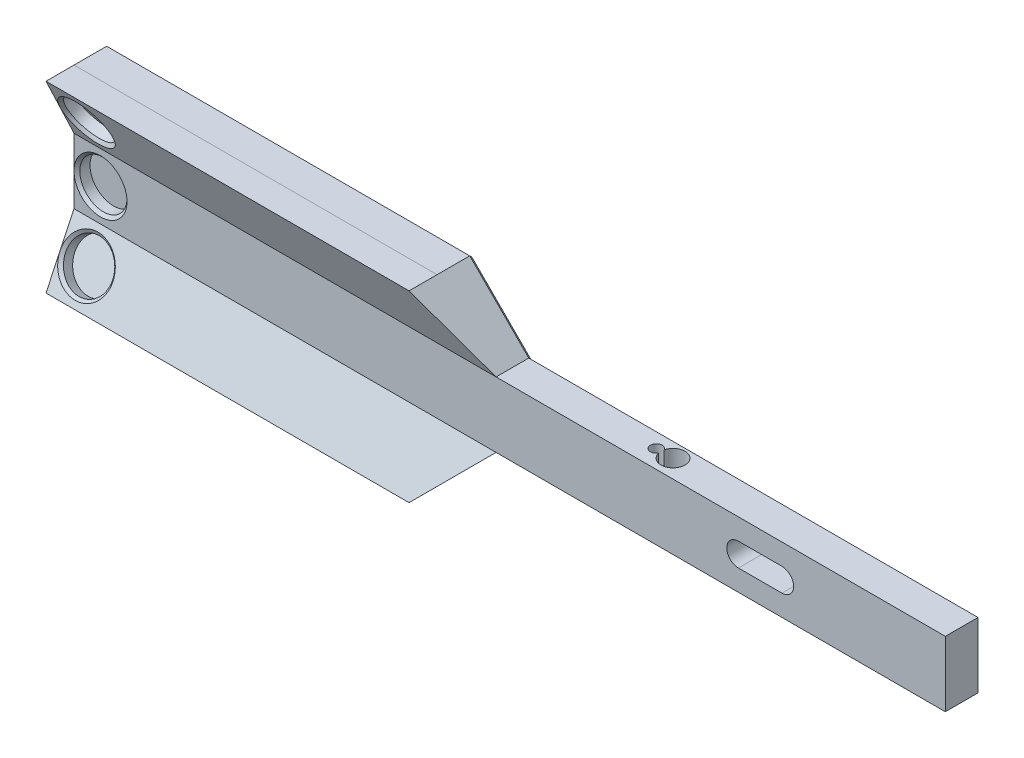
SolidWorks part; units mm, degrees
ref_plane "Front" through (0, 0, 0) normal (0, 0, 1) x (1, 0, 0)
ref_plane "Top" through (0, 0, 0) normal (0, 1, 0) x (1, 0, 0)
ref_plane "Right" through (0, 0, 0) normal (1, 0, 0) x (0, 0, -1)
sketch "Sketch1" plane through (0, 0, 0) normal (0, 0, 1) x (1, 0, 0)
  line L1 (60, -4.5) -> (-60, -4.5)
  line L2 (60, -4.5) -> (60, 4.5)
  line L3 (60, 4.5) -> (-60, 4.5)
  line L4 (-60, -4.5) -> (-60, 4.5)
  line L5 (60, -4.5) -> (-60, 4.5) construction
  line L6 (60, 4.5) -> (-60, -4.5) construction
  point P0 (0, 0)
  dimension "D1" = 9
  dimension "D2" = 120
extrude "Boss-Extrude1" add sketch "Sketch1" along normal blind 5
sketch "Sketch2" plane through (0, 4.5, 0) normal (0, 1, 0) x (1, 0, 0)
  line L0 (60, -5) -> (60, 0) construction
  line L2 (60, 0) -> (-60, 0) construction
  circle A0 centre (20, -2.5) radius 1.65
  dimension "D3" = 3.3
  dimension "D1" = 2.5
  dimension "D2" = 40
sketch "Sketch4" plane through (0, 0, 5) normal (0, 0, 1) x (1, 0, 0)
  line L0 (31.5, 0) -> (37.5, 0) construction
  line L1 (31.5, 1.6) -> (37.5, 1.6)
  line L2 (31.5, -1.6) -> (37.5, -1.6)
  arc A0 (31.5, 1.6) -> (31.5, -1.6) centre (31.5, 0) ccw
  arc A1 (37.5, -1.6) -> (37.5, 1.6) centre (37.5, 0) ccw
  point P2 (34.5, 0)
  dimension "D1" = 1.6
  dimension "D2" = 34.5
  dimension "D3" = 6
extrude "Cut-Extrude1" cut sketch "Sketch4" against normal blind 5
sketch "Sketch8" plane through (0, 0, 0) normal (0, 0, -1) x (-1, 0, 0)
  line L0 (60, 4.5) -> (60, -4.5) construction
  line L1 (60, 12.63) -> (10, 12.63)
  line L2 (60, 12.63) -> (60, -12.63)
  line L3 (60, -12.63) -> (10, -12.63)
  line L4 (10, 12.63) -> (10, -12.63)
  line L6 (-60, 4.5) -> (60, 4.5) construction
  dimension "D1" = 25.26
  dimension "D2" = 8.13
  dimension "D3" = 50
extrude "Boss-Extrude3" add sketch "Sketch8" against normal up to surface (5 mm away) up to face at (34.5, 0, 5)
sketch "Sketch9" plane through (-60, 0, 0) normal (-1, 0, 0) x (0, 0, 1)
  line L0 (5, 12.63) -> (5, -12.63) construction
  line L1 (5, 12.6327) -> (8.8548, 12.6327)
  line L2 (8.8548, 12.6327) -> (5, 4.5)
  line L3 (5, 4.5) -> (5, 12.6327)
  line L4 (-3.9634, 0) -> (12.9509, 0) construction
  line L5 (8.8548, -12.6327) -> (5, -4.5)
  line L6 (5, -12.6327) -> (8.8548, -12.6327)
  line L7 (5, -4.5) -> (5, -12.6327)
  circle A0 centre (25, 0) radius 20 construction
  dimension "D1" = 40
  dimension "D2" = 9
  dimension "D3" = 9
extrude "Boss-Extrude4" add sketch "Sketch9" against normal up to surface (50 mm away) up to face at (-10, 8.565, 2.5)
chamfer "Chamfer4" distance 8.13 2 edges at (-10, 4.5, 2.5) (-10, -4.5, 2.5)
chamfer "Chamfer1" distance 0.5 angle 45 12 edges at (60, 0, 0) (29.065, 4.5, 0) (-60, 0, 0) (29.065, -4.5, 0) (39.1, 0, 0) (34.5, -1.6, 0) (29.9, 0, 0) (34.5, 1.6, 0) (-35, 12.63, 0) (-35, -12.63, 0) (-5.935, 8.565, 0) (-5.935, -8.565, 0)
sketch "Sketch10" plane through (-60, 0, 0) normal (-1, 0, 0) x (0, 0, 1)
  line L0 (5, 4.5) -> (5, -4.5) construction
  line L1 (5, 4.5) -> (8.8548, 12.6327) construction
  line L2 (8.8548, -12.6327) -> (5, -4.5) construction
  circle A0 centre (25, 0) radius 20
sketch "Sketch11" plane through (0, 0, 5) normal (0, 0, 1) x (1, 0, 0)
  line L2 (-60, 4.5) -> (-60, -4.5) construction
  circle A0 centre (-56.35, 0) radius 3.25
  dimension "D1" = 6.5
  dimension "D2" = 3.65
extrude "Cut-Extrude3" cut sketch "Sketch11" against normal blind 1.8
sketch "Sketch12" plane through (0, -1.1096, 2.341) normal (0, -0.4283, 0.9036) x (1, 0, 0)
  line L1 (-10, 15.2079) -> (-60, 15.2079) construction
  line L2 (-60, 30.7079) -> (-60, -9.2921) construction
  circle A0 centre (-56.35, 10.7079) radius 3.25
  dimension "D1" = 6.5
  dimension "D2" = 4.5
  dimension "D3" = 3.65
extrude "Cut-Extrude4" cut sketch "Sketch12" against normal blind 1.8
mirror "Mirror2" about plane through (0, 0, 0) normal (0, 1, 0) of "Cut-Extrude4"
chamfer "Chamfer2" distance 0.4 angle 45 3 edges at (-53.1, 0, 5) (-56.35, -5.6295, 5.5354) (-56.35, 5.6295, 5.5354)
ref_plane "Plane1" through (-56, 0, 0) normal (-1, 0, 0) x (0, 0, 1)
extrude "Cut-Extrude5" cut sketch "Sketch2" against normal blind 10
sketch "Sketch13" plane through (60, 0, 0) normal (1, 0, 0) x (0, 0, -1)
  circle A0 centre (-2.5, -4.5) radius 0.8
  dimension "D1" = 1.6
  dimension "D2" = 2.5
  dimension "D3" = 4.5
extrude "Cut-Extrude6" cut sketch "Sketch13" against normal blind 25 from offset 40 offset against normal yes
sketch "Sketch14" plane through (0, -4.5, 0) normal (0, -1, 0) x (1, 0, 0)
  line L0 (59.5, 0) -> (-2.0771, 0) construction
  circle A0 centre (17.7, 2.5) radius 0.8
  arc A1 (18.5569, 1.7) -> (18.5569, 3.3) centre (20, 2.5) ccw construction
  dimension "D1" = 1.6
  dimension "D3" = 2.3
  dimension "D2" = 2.5
extrude "Cut-Extrude7" cut sketch "Sketch14" against normal blind 10
